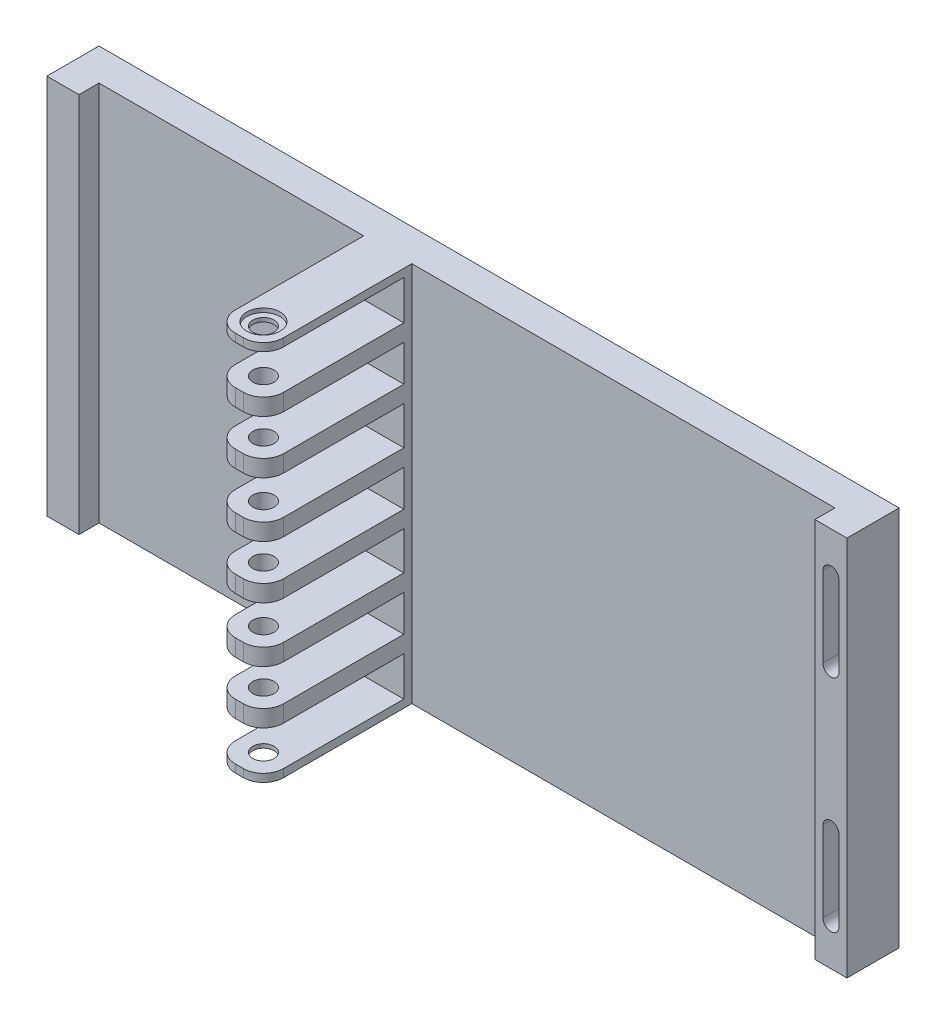
SolidWorks part; units mm, degrees
ref_plane "Front Plane" through (0, 0, 0) normal (1, 0, 0) x (0, 1, 0)
ref_plane "Top Plane" through (0, 0, 0) normal (0, 0, 1) x (0, 1, 0)
ref_plane "Right Plane" through (0, 0, 0) normal (0, 1, 0) x (-1, 0, 0)
sketch "Sketch1" plane through (0, 0, 0) normal (0, 0, 1) x (0, 1, 0)
  line L1 (0, 0) -> (-95, 0)
  line L2 (0, 0) -> (0, 12)
  line L3 (0, 12) -> (-95, 12)
  line L4 (-95, 0) -> (-95, 12)
extrude "Boss-Extrude1" add sketch "Sketch1" along normal blind 10 contours L3 L4 L1 L2
sketch "Sketch3" plane through (0, 0, 10) normal (0, 0, 1) x (1, 0, 0)
  line L0 (0, 0) -> (0, -95) construction
  line L1 (-12, 0) -> (0, 0)
  line L2 (-12, 0) -> (-12, -1.975)
  line L3 (-12, -1.975) -> (0, -1.975)
  line L4 (0, 0) -> (0, -1.975)
  line L6 (-12, -1.975) -> (0, -1.975) construction
  line L8 (-12, -11.775) -> (0, -11.775) construction
  line L10 (-12, -11.775) -> (0, -11.775)
  line L11 (-12, -11.775) -> (-12, -15.975)
  line L12 (-12, -15.975) -> (0, -15.975)
  line L13 (0, -11.775) -> (0, -15.975)
  line L14 (-12, -15.975) -> (0, -15.975) construction
  line L16 (-12, -25.025) -> (0, -25.025) construction
  line L18 (0, -25.025) -> (-12, -25.025)
  line L19 (0, -25.025) -> (0, -29.225)
  line L20 (0, -29.225) -> (-12, -29.225)
  line L21 (-12, -25.025) -> (-12, -29.225)
  line L23 (-12, -29.225) -> (0, -29.225) construction
  line L25 (-12, -38.775) -> (0, -38.775) construction
  line L27 (-12, -38.775) -> (0, -38.775)
  line L28 (-12, -38.775) -> (-12, -42.975)
  line L29 (-12, -42.975) -> (0, -42.975)
  line L30 (0, -38.775) -> (0, -42.975)
  point P4 (-12.0107, 0.2717)
  point P5 (-12, 0)
  point P6 (0, -11.594)
  dimension "D1" = 1.975
  dimension "D2" = 9.8
  dimension "D3" = 4.2
  dimension "D4" = 9.05
  dimension "D5" = 4.2
  dimension "D6" = 9.55
  dimension "D7" = 4.2
extrude "Boss-Extrude2" add sketch "Sketch3" along normal blind 35
fillet "Fillet1" radius 5 8 edges at (-12, -0.9875, 45) (0, -0.9875, 45) (-12, -13.875, 45) (0, -13.875, 45) (-12, -40.875, 45) (-12, -27.125, 45) (0, -27.125, 45) (0, -40.875, 45)
ref_plane "Plane1" through (0, -47.5, 0) normal (0, 1, 0) x (1, 0, 0)
mirror "Mirror1" about plane through (0, -47.5, 0) normal (0, 1, 0) of "Fillet1", "Boss-Extrude2"
sketch "Sketch5" plane through (0, 0, 0) normal (0, 1, 0) x (-1, 0, 0)
  line L0 (5, 45) -> (7, 45) construction
  line L1 (6, 45) -> (0, 45)
  line L2 (6, 45) -> (6, 39)
  line L3 (6, 39) -> (0, 39)
  line L4 (0, 45) -> (0, 39)
  circle A0 centre (6, 39) radius 2.65
  dimension "D1" = 6
extrude "Cut-Extrude1" cut sketch "Sketch5" against normal through all contours A0
sketch "Sketch7" plane through (0, 0, 0) normal (0, 1, 0) x (-1, 0, 0)
  line L0 (5, 45) -> (7, 45) construction
  line L1 (6, 45) -> (0, 45)
  line L2 (6, 45) -> (6, 39)
  line L3 (6, 39) -> (0, 39)
  line L4 (0, 45) -> (0, 39)
  line L5 (0, 40) -> (0, 0) construction
  circle A0 centre (6, 39) radius 4.15
  circle M6 centre (6, 39) radius 2.65
  dimension "D1" = 6
extrude "Cut-Extrude2" cut sketch "Sketch7" against normal blind 1 contours L3 A0 L2 M6 | L2 A0 L3 M6 region at (-8.8515, 0, 41.8515) region at (-3.8004, 0, 41.1996)
mirror "Mirror2" about plane through (0, -47.5, 0) normal (0, 1, 0) of "Cut-Extrude2"
sketch "Sketch8" plane through (0, 0, 0) normal (0, 0, -1) x (1, 0, 0)
  line L0 (0, 95) -> (-12, 95) construction
  line L1 (-6, 95) -> (-86, 95)
  line L2 (-6, 95) -> (-6, 0)
  line L3 (-6, 0) -> (-86, 0)
  line L4 (-86, 95) -> (-86, 0)
  line L5 (-6, 95) -> (113.5, 95)
  line L6 (-6, 95) -> (-6, 0)
  line L7 (-6, 0) -> (113.5, 0)
  line L8 (113.5, 95) -> (113.5, 0)
  line L9 (0, 0) -> (-12, 0) construction
  point P4 (0, 0)
  point P7 (0, 0)
  point P8 (-6, 95.25)
  point P11 (-6, 0)
  line M2 (0, 0) -> (0, 95)
  line M4 (-12, 95) -> (-12, 0)
extrude "Boss-Extrude3" add sketch "Sketch8" against normal blind 8 contours L1 L4 L3 M4 | L8 L5 L7 M2 region at (-49, -47.5, 0) region at (56.75, -47.5, 0)
sketch "Sketch9" plane through (0, 0, 8) normal (0, 0, 1) x (1, 0, 0)
  line L0 (0, -95) -> (113.5, -95) construction
  line L1 (113.5, 0) -> (105.5, 0)
  line L2 (113.5, 0) -> (113.5, -95)
  line L3 (113.5, -95) -> (105.5, -95)
  line L4 (105.5, 0) -> (105.5, -95)
  line L5 (-12, -95) -> (-86, -95) construction
  line L6 (-86, 0) -> (-78, 0)
  line L7 (-86, 0) -> (-86, -95)
  line L8 (-86, -95) -> (-78, -95)
  line L9 (-78, 0) -> (-78, -95)
  dimension "D1" = 8
  dimension "D2" = 8
extrude "Boss-Extrude4" add sketch "Sketch9" along normal blind 5
sketch "Sketch11" plane through (0, 0, 13) normal (0, 0, 1) x (1, 0, 0)
  line L0 (109.5, 0) -> (109.5, -95) construction
  line L1 (113.5, 0) -> (105.5, 0) construction
  line L2 (105.5, -95) -> (113.5, -95) construction
  line L3 (109.5, -10) -> (109.5, -30) construction
  line L4 (111.5, -10) -> (111.5, -30)
  line L5 (107.5, -10) -> (107.5, -30)
  line L7 (113.5, 0) -> (109.5, 0)
  line L8 (113.5, 0) -> (113.5, -10)
  line L9 (113.5, -10) -> (109.5, -10)
  line L10 (109.5, 0) -> (109.5, -10)
  arc A0 (111.5, -10) -> (107.5, -10) centre (109.5, -10) ccw
  arc A1 (107.5, -30) -> (111.5, -30) centre (109.5, -30) ccw
  point P8 (109.5, -20)
  point P16 (109.5, -33.6172)
  point P18 (109.5, -26.3368)
  point P19 (0, 0)
  dimension "D1" = 10
  dimension "D2" = 20
extrude "Cut-Extrude3" cut sketch "Sketch11" against normal blind 10 contours L4 A1 L5 A0
pattern_linear "LPattern1" count 2 spacing 55 along (0, -1, 0) of "Cut-Extrude3"
equation "\"whitekey_cutout_length\"= 101.5"
equation "\"mount_recess_length\"=50"
equation "\"mount_recess_height\"=12.5"
equation "\"mount_recess_depth\"=1.5"
equation "\"wall_thickness\"=8"
equation "\"D1@Sketch9\"=\"wall_thickness\""
equation "\"D2@Sketch9\"=\"wall_thickness\""
equation "\"D1@Boss-Extrude3\"=\"wall_thickness\""
